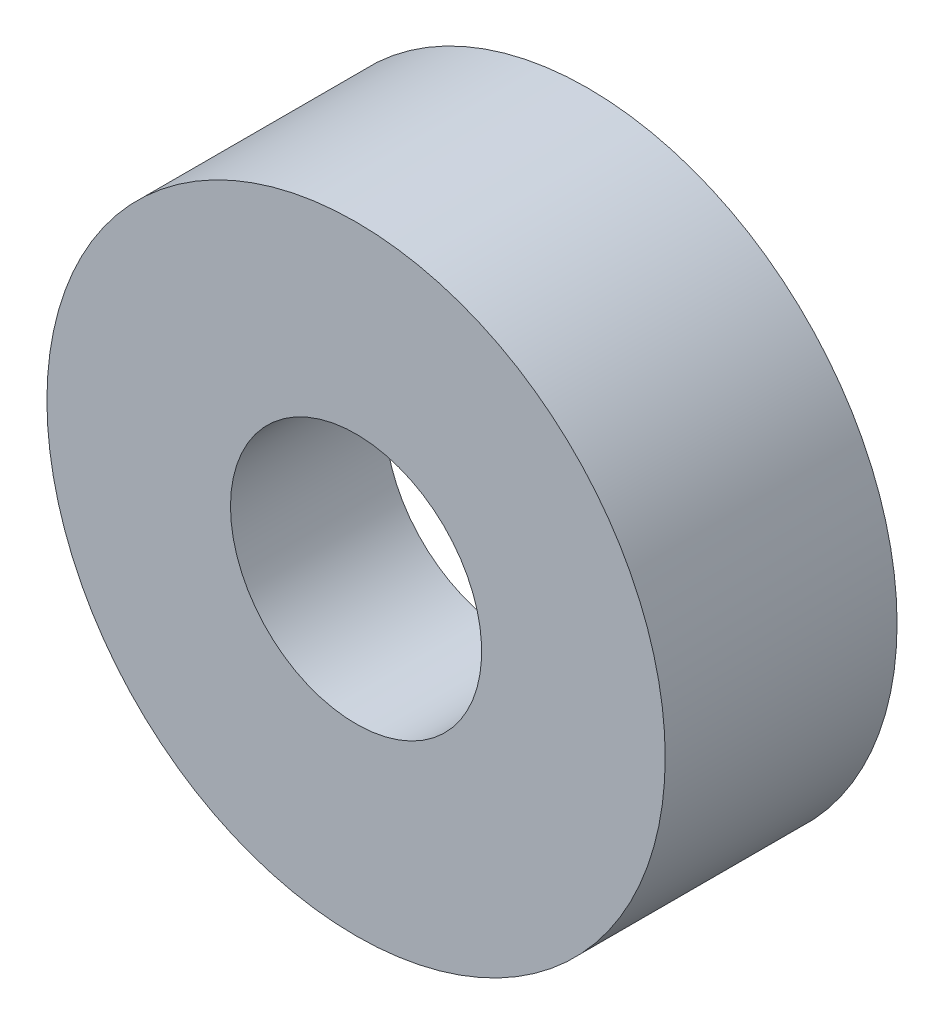
SolidWorks part; units mm, degrees
ref_plane "Front Plane" through (0, 0, 0) normal (0, 0, 1) x (1, 0, 0)
ref_plane "Top Plane" through (0, 0, 0) normal (0, 1, 0) x (1, 0, 0)
ref_plane "Right Plane" through (0, 0, 0) normal (1, 0, 0) x (0, 0, -1)
sketch "Sketch2" plane through (0, 0, 0) normal (0, 1, 0) x (1, 0, 0)
  line L0 (0, 0) -> (4.75, 0)
  line L1 (4.75, 0) -> (4.75, 4)
  line L2 (4.75, 4) -> (3, 4)
  line L3 (0, 0) -> (0, 6)
  line L4 (8, 7.218) -> (8, 0) construction
  arc A0 (0, 6) -> (3, 4) centre (4.0869, 8.8804) ccw
  dimension "D7" = 5
  dimension "D1" = 3.25
  dimension "D2" = 8
  dimension "D3" = 4.75
  dimension "D4" = 4
  dimension "D5" = 6
  dimension "D6" = 3
revolve "Revolve1" add sketch "Sketch2" angle 360 about L4
